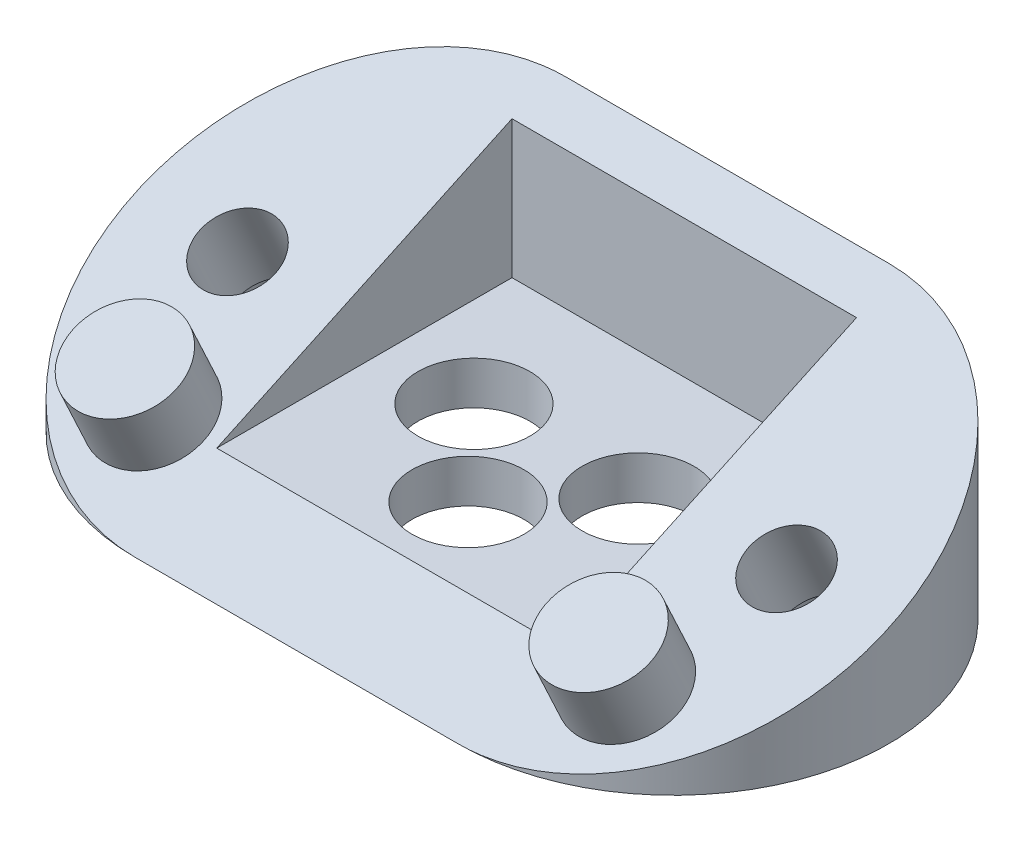
SolidWorks part; units mm, degrees
ref_plane "Front Plane" through (0, 0, 0) normal (0, 0, 1) x (1, 0, 0)
ref_plane "Top Plane" through (0, 0, 0) normal (0, 1, 0) x (1, 0, 0)
ref_plane "Right Plane" through (0, 0, 0) normal (1, 0, 0) x (0, 0, -1)
sketch "Sketch1" plane through (0, 0, 0) normal (0, 1, 0) x (1, 0, 0)
  line L0 (-7.5, 0) -> (7.5, 0) construction
  line L1 (-7.5, 10) -> (7.5, 10)
  line L2 (-7.5, -10) -> (7.5, -10)
  line L3 (-3.81, 2.0429) -> (3.81, 2.0429) construction
  line L4 (0, -2.0429) -> (-3.81, 2.0429) construction
  line L5 (0, -2.0429) -> (3.81, 2.0429) construction
  line L6 (0, -2.0429) -> (0, 2.0429) construction
  arc A0 (-7.5, 10) -> (-7.5, -10) centre (-7.5, 0) ccw
  arc A1 (7.5, -10) -> (7.5, 10) centre (7.5, 0) ccw
  circle A2 centre (-3.81, 2.0429) radius 2.6
  circle A3 centre (3.81, 2.0429) radius 2.6
  circle A4 centre (0, -2.0429) radius 2.6
  point P2 (0, 0)
  point P13 (0, 0)
  point P15 (0, 2.0429)
  dimension "D2" = 10
  dimension "D3" = 5.2
  dimension "D4" = 5.2
  dimension "D5" = 5.2
  dimension "D1" = 15
  dimension "D6" = 7.62
  dimension "D7" = 47
  dimension "D8" = 47
extrude "Boss-Extrude3" add sketch "Sketch1" along normal blind 20
sketch "Sketch2" plane through (0, 20, 0) normal (0, 1, 0) x (1, 0, 0)
  line L1 (-8, 8) -> (8, 8)
  line L2 (-8, 8) -> (-8, -8)
  line L3 (-8, -8) -> (8, -8)
  line L4 (8, 8) -> (8, -8)
  line L5 (-8, 8) -> (8, -8) construction
  line L6 (-8, -8) -> (8, 8) construction
  point P0 (0, 0)
  dimension "D1" = 16
  dimension "D2" = 16
extrude "Cut-Extrude1" cut sketch "Sketch2" against normal offset from surface (18 mm away) 2 up to face at (0, 0, 0)
sketch "Sketch4" plane through (-8, 0, 0) normal (1, 0, 0) x (0, 0, -1)
  line L0 (-10, 0) -> (10, 9.3262)
  line L1 (10, 20) -> (10, 0) construction
  line L6 (-10, 0) -> (10, 0)
  line L7 (-10, 20) -> (-10, 0)
  line L8 (10, 20) -> (-10, 20)
  line L9 (10, 0) -> (10, 20)
  line L10 (-10, 0) -> (10, 0)
  line L11 (-10, 20) -> (-10, 0)
  line L12 (10, 20) -> (-10, 20)
  line L13 (10, 0) -> (10, 20)
  line M6 (-8, 2) -> (8, 2)
  line M7 (8, 2) -> (8, 20)
  line M8 (8, 20) -> (-8, 20)
  line M9 (-8, 20) -> (-8, 2)
  dimension "D2" = 65
  dimension "D1" = 0
extrude "Cut-Extrude2" cut sketch "Sketch4" against normal through all both and the other way through all contours L0 M6 M7 M8 M9 | L0 L13 L12 M7 | L12 L11 L0 M9 M6 region at (-8, 9.9709, 8.9543) region at (-8, 12.233, 0.6157) region at (-8, 14.4267, -8.986)
sketch "Sketch5" plane through (0, 3.8302, 1.7861) normal (0, 0.9063, 0.4226) x (1, 0, 0)
  line L0 (-12.75, 1.9707) -> (-17.5, 1.9707) construction
  line L1 (-12.75, 1.9707) -> (-8, 1.9707) construction
  line L2 (-8, 10.7977) -> (-8, -4.3307) construction
  line L3 (0, -9.0631) -> (0, 13.0045) construction
  line L4 (-7.5, -9.0631) -> (7.5, -9.0631) construction
  line L5 (-7.5, 13.0045) -> (7.5, 13.0045) construction
  circle A0 centre (-12.75, 1.9707) radius 1.75
  circle A2 centre (12.75, 1.9707) radius 1.75
  dimension "D1" = 3.5
extrude "Cut-Extrude3" cut sketch "Sketch5" against normal through all and the other way through all
sketch "Sketch7" plane through (0, 3.8302, 1.7861) normal (0, 0.9063, 0.4226) x (1, 0, 0)
  line L0 (0, 13.0045) -> (0, -9.0631) construction
  line L1 (-7.5, 13.0045) -> (7.5, 13.0045) construction
  line L2 (-7.5, -9.0631) -> (7.5, -9.0631) construction
  circle A0 centre (-12.75, 1.9707) radius 2.5
  circle A1 centre (12.75, 1.9707) radius 2.5
  circle A2 centre (12.75, 1.9707) radius 1.75 construction
  circle A3 centre (-12.75, 1.9707) radius 1.75 construction
  circle A4 centre (12.75, 1.9707) radius 1.75
  circle A5 centre (-12.75, 1.9707) radius 1.75
  dimension "D1" = 5
extrude "Boss-Extrude4" add sketch "Sketch7" against normal blind 4
extrude "Cut-Extrude6" cut sketch "Sketch7<5>" against normal up to surface (0.3291 mm away) from offset 4 contours A4 | A1 | A5 | A0 up to face at (12.75, 0, 0.5596) offset against normal yes
sketch "Sketch7<5>" plane through (0, 3.8302, 1.7861) normal (0, 0.9063, 0.4226) x (1, 0, 0) same geometry as "Sketch7"
sketch "Sketch9" plane through (0, 3.8302, 1.7861) normal (0, 0.9063, 0.4226) x (1, 0, 0)
  line L0 (8, -4.3307) -> (-8, -4.3307) construction
  line L1 (-11, -4.3307) -> (-8, -4.3307) construction
  line L2 (0, -9.0631) -> (0, 13.0045) construction
  line L3 (-7.5, -9.0631) -> (7.5, -9.0631) construction
  line L4 (-7.5, 13.0045) -> (7.5, 13.0045) construction
  circle A0 centre (-11, -4.3307) radius 2.4
  circle A1 centre (11, -4.3307) radius 2.4
  dimension "D1" = 4.8
  dimension "D2" = 3
extrude "Boss-Extrude5" add sketch "Sketch9" along normal blind 3
equation "\"D4@Sketch1\"=\"D3@Sketch1\""
equation "\"D5@Sketch1\"=\"D3@Sketch1\""
